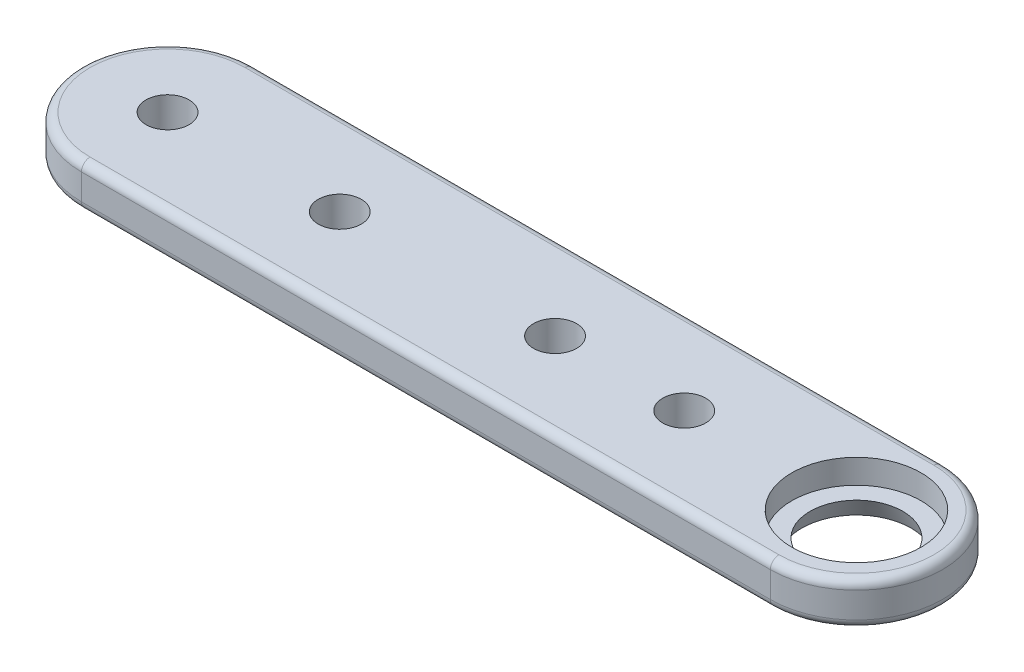
SolidWorks part; units mm, degrees
material "Plain Carbon Steel"
ref_plane "Front Plane" through (0, 0, 0) normal (0, 0, 1) x (1, 0, 0)
ref_plane "Top Plane" through (0, 0, 0) normal (0, 1, 0) x (1, 0, 0)
ref_plane "Right Plane" through (0, 0, 0) normal (1, 0, 0) x (0, 0, -1)
sketch "Sketch1" plane through (0, 0, 0) normal (0, 1, 0) x (1, 0, 0)
  line L1 (63.5, -12.7) -> (-63.5, -12.7)
  line L2 (63.5, -12.7) -> (63.5, 12.7)
  line L3 (63.5, 12.7) -> (-63.5, 12.7)
  line L4 (-63.5, -12.7) -> (-63.5, 12.7)
  line L5 (63.5, -12.7) -> (-63.5, 12.7) construction
  line L6 (63.5, 12.7) -> (-63.5, -12.7) construction
  point P0 (0, 0)
  dimension "D1" = 25.4
  dimension "D2" = 127
extrude "Boss-Extrude1" add sketch "Sketch1" along normal blind 6.35
sketch "Sketch2" plane through (0, 6.35, 0) normal (0, 1, 0) x (1, 0, 0)
  line L0 (-63.5, 0) -> (63.5, 0) construction
  line L1 (-63.5, 12.7) -> (-63.5, -12.7) construction
  line L2 (63.5, -12.7) -> (63.5, 12.7) construction
  circle A0 centre (-50.8, 0) radius 3.175
  circle A3 centre (50.8, 0) radius 6.35
  circle A7 centre (-25.4, 0) radius 3.175
  dimension "D1" = 12.7
  dimension "D4" = 6.35
  dimension "D2" = 101.6
  dimension "D3" = 12.7
  dimension "D5" = 2
extrude "Cut-Extrude1" cut sketch "Sketch2" against normal through all
sketch "Sketch3" plane through (0, 6.35, 0) normal (0, 1, 0) x (1, 0, 0)
  circle A0 centre (50.8, 0) radius 9.525
  dimension "D1" = 19.05
extrude "Cut-Extrude2" cut sketch "Sketch3" against normal blind 3.5719
sketch "Sketch4" plane through (0, 6.35, 0) normal (0, 1, 0) x (1, 0, 0)
  line L0 (-63.5, 0) -> (63.5, 0) construction
  circle A0 centre (25.4, 0) radius 3.175
  circle A2 centre (6.35, 0) radius 3.175
  dimension "D3" = 6.35
  dimension "D1" = 25.4
  dimension "D2" = 19.05
extrude "Cut-Extrude3" cut sketch "Sketch4" against normal through all
sketch "Sketch5" plane through (0, 6.35, 0) normal (0, 1, 0) x (1, 0, 0)
  line L0 (63.5, -12.7) -> (63.5, 12.7) construction
  line L3 (-63.5, 12.7) -> (-63.5, -12.7) construction
  circle A2 centre (-50.8, 0) radius 12.7
  circle A3 centre (50.8, 0) radius 12.7
  line M11 (63.5, -12.7) -> (63.5, 12.7)
  line M13 (-63.5, 12.7) -> (-63.5, -12.7)
  line M25 (-63.5, -12.7) -> (63.5, -12.7)
  line M26 (63.5, 12.7) -> (-63.5, 12.7)
extrude "Cut-Extrude4" cut sketch "Sketch5" against normal through all contours A3 M11 M26 | A3 M25 M11 | A2 M26 M13 | A2 M13 M25 region at (-60.6632, 6.35, -9.8632) region at (-60.6632, 6.35, 9.8632) region at (60.6632, 6.35, -9.8632) region at (60.6632, 6.35, 9.8632)
fillet "Fillet1" radius 1.27 8 edges at (0, 0, -12.7) (0, 6.35, -12.7) (0, 0, 12.7) (0, 6.35, 12.7) (-63.5, 0, 0) (-63.5, 6.35, 0) (63.5, 0, 0) (63.5, 6.35, 0)
ref_axis "Axis1" through (50.8, 0, 0) along (0, 1, 0)
ref_plane "Plane1" through (50.8, 0, 0) normal (-1, 0, 0) x (0, 0, 1)
sketch "Sketch6" plane through (50.8, 0, 0) normal (-1, 0, 0) x (0, 0, 1)
  line L0 (0, 0) -> (0, 6.35)
  line L1 (11.43, 6.35) -> (-11.43, 6.35) construction
  line L2 (0, 6.35) -> (-3.6942, -1.9474)
  line L3 (-3.6942, -1.9474) -> (-8.0682, 0)
  line L4 (-8.0682, 0) -> (-4.374, 8.2974)
  line L5 (-4.374, 8.2974) -> (0, 6.35)
  line L6 (-11.43, 0) -> (11.43, 0) construction
  line L7 (0, 0) -> (-6.35, 0)
  line L8 (-6.35, 0) -> (-6.35, 2.7781)
  line L9 (-6.35, 2.7781) -> (0, 2.7781)
  line L10 (-6.35, 0) -> (-8.0682, 0)
  line L11 (-6.35, 2.7781) -> (-6.8313, 2.7781)
  dimension "D1" = 24
  dimension "D2" = 4.7879
  dimension "D3" = 6.35
  dimension "D4" = 2.7781
revolve "Cut-Revolve2" cut sketch "Sketch6" angle 360 about axis through (50.8, 0, 0) along (0, 1, 0) region at (50.8, 1.1287, -6.9578)
